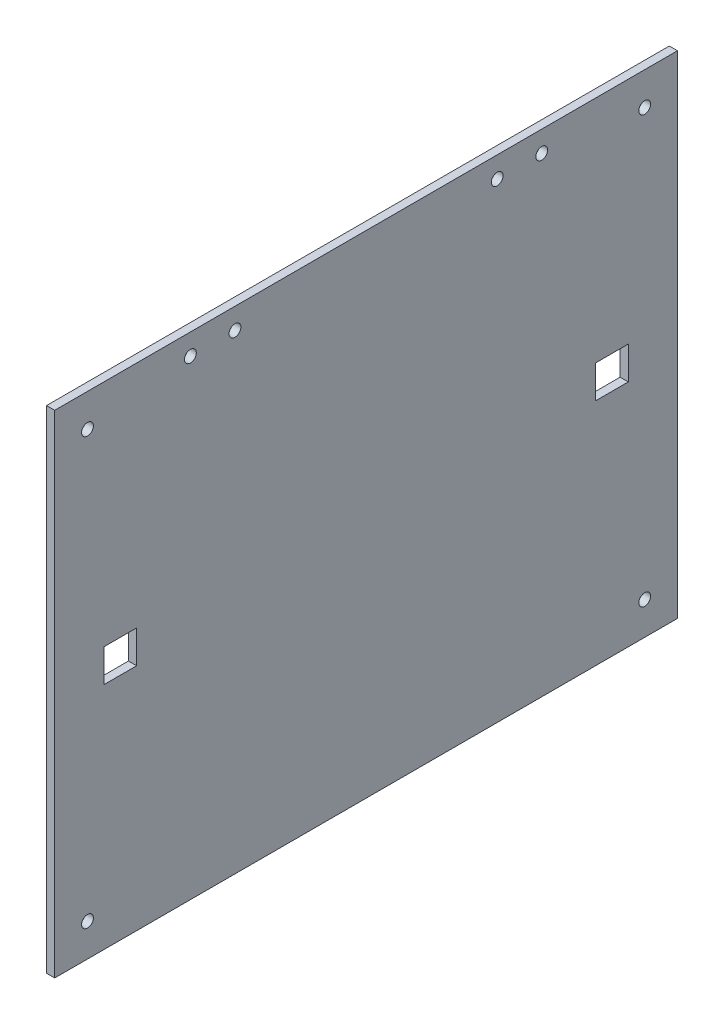
SolidWorks part; units mm, degrees
ref_plane "Front Plane" through (0, 0, 0) normal (0, 0, 1) x (1, 0, 0)
ref_plane "Top Plane" through (0, 0, 0) normal (0, 1, 0) x (1, 0, 0)
ref_plane "Right Plane" through (0, 0, 0) normal (1, 0, 0) x (0, 0, -1)
sketch "Sketch1" plane through (0, 0, 0) normal (1, 0, 0) x (0, 0, -1)
  line L1 (0, 0) -> (241.3, 0)
  line L2 (0, 0) -> (0, 190.5)
  line L3 (0, 190.5) -> (241.3, 190.5)
  line L4 (241.3, 0) -> (241.3, 190.5)
  dimension "D1" = 241.3
  dimension "D2" = 190.5
extrude "Boss-Extrude1" add sketch "Sketch1" along normal blind 3.175
sketch "Sketch2" plane through (3.175, 0, 0) normal (1, 0, 0) x (0, 0, -1)
  line L2 (-1000, 95.25) -> (49000, 95.25) construction
  line L3 (0, 190.5) -> (0, 0) construction
  line L4 (120.65, -809.5) -> (120.65, 49190.5) construction
  line L5 (241.3, 190.5) -> (0, 190.5) construction
  line L6 (1228.6, 95.25) -> (-48771.4, 95.25) construction
  line L7 (0, 0) -> (241.3, 0) construction
  line L8 (241.3, 0) -> (241.3, 190.5) construction
  circle A8 centre (228.6, 12.7) radius 2.286
  circle A9 centre (228.6, 177.8) radius 2.286
  circle A10 centre (12.7, 12.7) radius 2.286
  circle A11 centre (12.7, 177.8) radius 2.286
  point P15 (0, 95.25)
  point P20 (120.65, 190.5)
  dimension "D1" = 4.572
  dimension "D2" = 12.7
  dimension "D3" = 12.7
extrude "Cut-Extrude1" cut sketch "Sketch2" against normal through all
sketch "Sketch3" plane through (3.175, 0, 0) normal (1, 0, 0) x (0, 0, -1)
  line L0 (54.864, 182.372) -> (67.564, 182.372) construction
  line L1 (173.736, 182.372) -> (186.436, 182.372) construction
  line L2 (241.3, 190.5) -> (0, 190.5) construction
  circle A0 centre (52.578, 182.372) radius 2.286
  circle A1 centre (69.85, 182.372) radius 2.286
  circle A2 centre (171.45, 182.372) radius 2.286
  circle A3 centre (188.722, 182.372) radius 2.286
  point P14 (120.65, 190.5)
  dimension "D2" = 4.572
  dimension "D1" = 12.7
  dimension "D3" = 12.7
  dimension "D4" = 8.128
  dimension "D5" = 50.8
  dimension "D6" = 50.8
extrude "Cut-Extrude2" cut sketch "Sketch3" against normal through all
sketch "Sketch4" plane through (3.175, 0, 0) normal (1, 0, 0) x (0, 0, -1)
  line L0 (0, 190.5) -> (0, 0) construction
  line L1 (19.05, 101.6) -> (31.75, 101.6)
  line L2 (19.05, 101.6) -> (19.05, 88.9)
  line L3 (19.05, 88.9) -> (31.75, 88.9)
  line L4 (31.75, 101.6) -> (31.75, 88.9)
  line L5 (209.55, 88.9) -> (222.25, 88.9)
  line L6 (209.55, 88.9) -> (209.55, 101.6)
  line L7 (209.55, 101.6) -> (222.25, 101.6)
  line L8 (222.25, 88.9) -> (222.25, 101.6)
  line L9 (241.3, 0) -> (241.3, 190.5) construction
  point P8 (19.05, 95.25)
  point P11 (0, 95.25)
  point P12 (209.55, 95.25)
  dimension "D1" = 12.7
  dimension "D2" = 12.7
  dimension "D3" = 19.05
  dimension "D4" = 19.05
extrude "Cut-Extrude3" cut sketch "Sketch4" against normal through all
